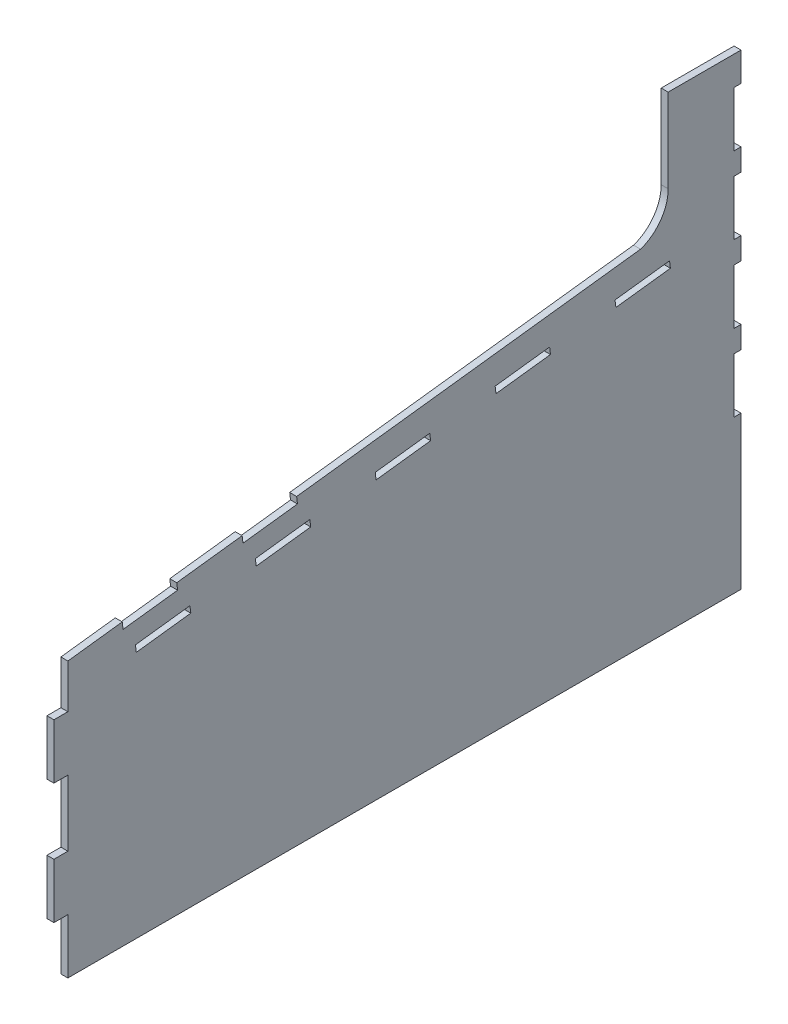
SolidWorks part; units mm, degrees
material "Beech"
ref_plane "Front Plane" through (0, 0, 0) normal (0, 0, 1) x (1, 0, 0)
ref_plane "Top Plane" through (0, 0, 0) normal (0, 1, 0) x (1, 0, 0)
ref_plane "Right Plane" through (0, 0, 0) normal (1, 0, 0) x (0, 0, -1)
sketch "Sketch1" plane through (0, 0, 0) normal (1, 0, 0) x (0, 0, -1)
  line L1 (0, 0) -> (613, 0)
  line L2 (0, 0) -> (0, 50)
  line L4 (613, 0) -> (613, 138.97)
  line L6 (613, 258.97) -> (613, 278.97)
  line L7 (613, 425.32) -> (546.65, 425.32)
  line L8 (546.65, 349.09) -> (546.65, 425.32)
  line L9 (0, 250) -> (613, 250) construction
  line L10 (521.4684, 314.0283) -> (613, 325.2669) construction
  line L11 (-12.7, 160) -> (-12.7, 210)
  line L12 (0, 50) -> (-12.7, 50)
  line L14 (0, 100) -> (-12.7, 100)
  line L15 (-12.7, 50) -> (-12.7, 100)
  line L16 (0, 160) -> (-12.7, 160)
  line L18 (0, 210) -> (-12.7, 210)
  line L19 (0, 210) -> (0, 250)
  line L21 (0, 100) -> (0, 160)
  line L33 (0, 250) -> (521.4684, 314.0283) construction
  line L34 (0, 250) -> (521.4684, 314.0283)
  line L36 (613, 398.97) -> (606.65, 398.97)
  line L38 (613, 348.97) -> (606.65, 348.97)
  line L39 (606.65, 398.97) -> (606.65, 348.97)
  line L40 (613, 328.97) -> (606.65, 328.97)
  line L41 (606.65, 328.97) -> (606.65, 278.97)
  line L42 (613, 278.97) -> (606.65, 278.97)
  line L44 (613, 258.97) -> (606.65, 258.97)
  line L45 (606.65, 258.97) -> (606.65, 208.97)
  line L46 (613, 208.97) -> (606.65, 208.97)
  line L48 (613, 188.97) -> (606.65, 188.97)
  line L49 (606.65, 188.97) -> (606.65, 138.97)
  line L50 (613, 138.97) -> (606.65, 138.97)
  line L51 (613, 188.97) -> (613, 208.97)
  line L54 (613, 328.97) -> (613, 348.97)
  line L56 (613, 398.97) -> (613, 425.32)
  arc A0 (521.4684, 314.0283) -> (546.65, 349.09) centre (509.65, 349.09) ccw
  dimension "D4" = 37
  dimension "D1" = 613
  dimension "D2" = 250
  dimension "D3" = 66.35
  dimension "D5" = 7
  dimension "D6" = 175.32
  dimension "D7" = 76.23
  dimension "D8" = 12.7
  dimension "D9" = 50
  dimension "D10" = 50
  dimension "D11" = 2
  dimension "D12" = 40
  dimension "D13" = 6.35
  dimension "D14" = 50
  dimension "D15" = 26.35
  dimension "D17" = 138.97
  dimension "D16" = 4
extrude "Boss-Extrude1" add sketch "Sketch1" along normal blind 6.35
sketch "Sketch2" plane through (6.35, 0, 0) normal (1, 0, 0) x (0, 0, -1)
  line L0 (514.5695, 313.1812) -> (613, 324.7758) construction
  line L1 (613, 0) -> (613, 138.97) construction
  line L2 (208.3168, 275.5781) -> (158.6895, 269.4846)
  line L3 (0, 224.4093) -> (613, 299.6762) construction
  line L4 (0, 50) -> (0, 0) construction
  line L5 (61.5379, 231.9651) -> (62.3117, 225.6625)
  line L6 (62.3117, 225.6625) -> (111.939, 231.7559)
  line L7 (111.939, 231.7559) -> (111.1652, 238.0586)
  line L8 (111.1652, 238.0586) -> (61.5379, 231.9651)
  line L9 (220.3452, 251.4642) -> (170.7179, 245.3708)
  line L10 (170.7179, 245.3708) -> (171.4918, 239.0681)
  line L11 (171.4918, 239.0681) -> (221.1191, 245.1616)
  line L12 (221.1191, 245.1616) -> (220.3452, 251.4642)
  line L13 (329.5253, 264.8699) -> (279.898, 258.7764)
  line L14 (279.898, 258.7764) -> (280.6719, 252.4737)
  line L15 (280.6719, 252.4737) -> (330.2992, 258.5672)
  line L16 (330.2992, 258.5672) -> (329.5253, 264.8699)
  line L17 (438.7054, 278.2755) -> (389.0781, 272.182)
  line L18 (389.0781, 272.182) -> (389.852, 265.8794)
  line L19 (389.852, 265.8794) -> (439.4793, 271.9728)
  line L20 (439.4793, 271.9728) -> (438.7054, 278.2755)
  line L21 (547.8855, 291.6811) -> (498.2582, 285.5877)
  line L22 (498.2582, 285.5877) -> (499.032, 279.285)
  line L23 (499.032, 279.285) -> (548.6593, 285.3785)
  line L24 (548.6593, 285.3785) -> (547.8855, 291.6811)
  line L25 (158.6895, 269.4846) -> (159.4634, 263.182)
  line L26 (521.4684, 314.0283) -> (0, 250) construction
  line L27 (0, 224.4093) -> (-3.0955, 249.6199) construction
  line L28 (-3.0955, 249.6199) -> (0, 250) construction
  line L29 (49.5095, 256.079) -> (50.2833, 249.7763)
  line L30 (50.2833, 249.7763) -> (99.9106, 255.8698)
  line L31 (99.9106, 255.8698) -> (99.1368, 262.1725)
  line L32 (99.1368, 262.1725) -> (49.5095, 256.079)
  line L33 (159.4634, 263.182) -> (209.0907, 269.2754)
  line L34 (209.0907, 269.2754) -> (208.3168, 275.5781)
  dimension "D1" = 25.4
  dimension "D2" = 50
  dimension "D3" = 6.35
  dimension "D4" = 62
  dimension "D5" = 90
  dimension "D6" = 6.35
  dimension "D7" = 53
  dimension "D8" = 50
  dimension "D9" = 2
extrude "Cut-Extrude1" cut sketch "Sketch2" against normal blind 6.35
